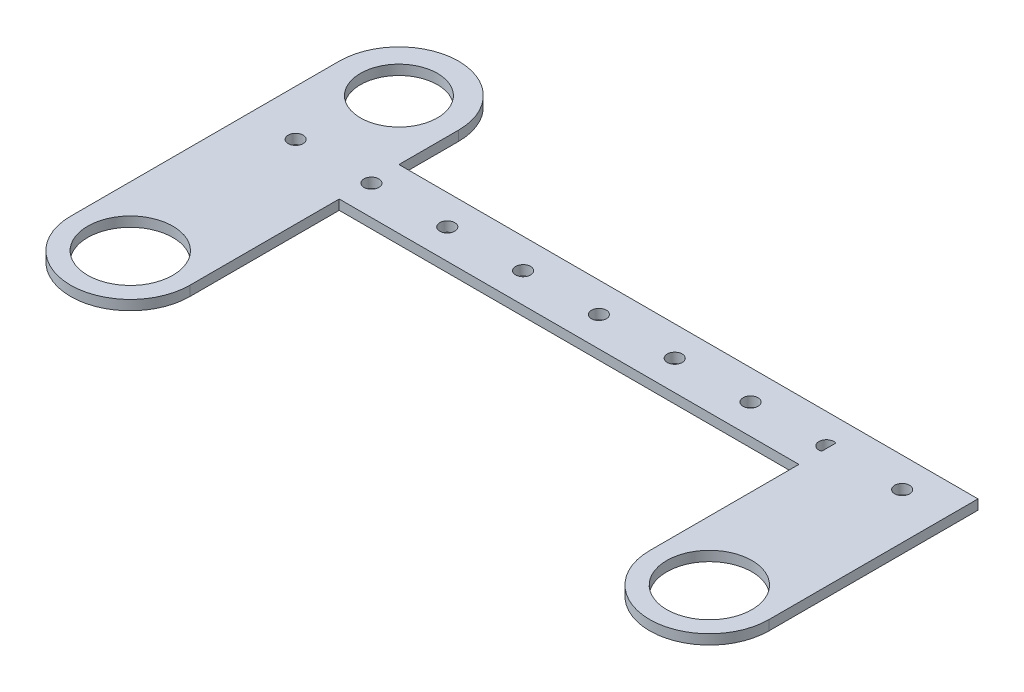
SolidWorks part; units mm, degrees
note: The reader was unsure of these and kept them because the rebuilt part matched: shared geometry of "Sketch1<3>".
ref_plane "Front Plane" through (0, 0, 0) normal (0, 0, 1) x (1, 0, 0)
ref_plane "Top Plane" through (0, 0, 0) normal (0, 1, 0) x (1, 0, 0)
ref_plane "Right Plane" through (0, 0, 0) normal (1, 0, 0) x (0, 0, -1)
sketch "Sketch1" plane through (0, 0, 0) normal (0, 1, 0) x (1, 0, 0)
  line L0 (0, 0) -> (0, 18.1373) construction
  line L1 (-117, -10) -> (117, -10)
  line L2 (-117, -10) -> (-117, 10)
  line L3 (-117, 10) -> (117, 10)
  line L4 (117, -10) -> (117, 10)
  line L5 (-117, -10) -> (117, 10) construction
  line L6 (-117, 10) -> (117, -10) construction
  line L7 (-117, 10) -> (-77, 10)
  line L8 (-117, 10) -> (-117, -60)
  line L11 (117, 10) -> (117, -60)
  line L12 (77, 10) -> (77, -60)
  line L13 (-117, 10) -> (-117, 30)
  line L14 (-77, 30) -> (-77, 10)
  line L15 (-77, -10) -> (-77, -60)
  circle A0 centre (-97, -60) radius 20
  circle A1 centre (-97, -60) radius 14.26
  circle A3 centre (97, -60) radius 14.26
  circle A4 centre (97, -60) radius 20
  arc A5 (-117, 30) -> (-77, 30) centre (-97, 30) cw
  circle A6 centre (0, 0) radius 2.5
  circle A7 centre (25.4, 0) radius 2.5
  circle A8 centre (50.8, 0) radius 2.5
  circle A9 centre (76.2, 0) radius 2.5
  circle A10 centre (101.6, 0) radius 2.5
  circle A11 centre (-25.4, 0) radius 2.5
  circle A12 centre (-50.8, 0) radius 2.5
  circle A13 centre (-76.2, 0) radius 2.5
  circle A14 centre (-101.6, 0) radius 2.5
  circle A15 centre (-97, 30) radius 12.91
  point P0 (0, 0)
  dimension "D5" = 40
  dimension "D6" = 28.52
  dimension "D7" = 20
  dimension "D3" = 5
  dimension "D4" = 25.82
  dimension "D1" = 20
  dimension "D2" = 234
  dimension "D8" = 5
  dimension "D9" = 5
extrude "Boss-Extrude1" add sketch "Sketch1" along normal blind 3.3
extrude "Saliente-Extruir1" add sketch "Sketch1<3>" along normal up to surface (3.3 mm away) contours A5 L13 L3 L14 A15 up to face at (75.35, 3.3, 0)
sketch "Sketch1<3>" plane through (0, 0, 0) normal (0, 1, 0) x (1, 0, 0) same geometry as "Sketch1"
